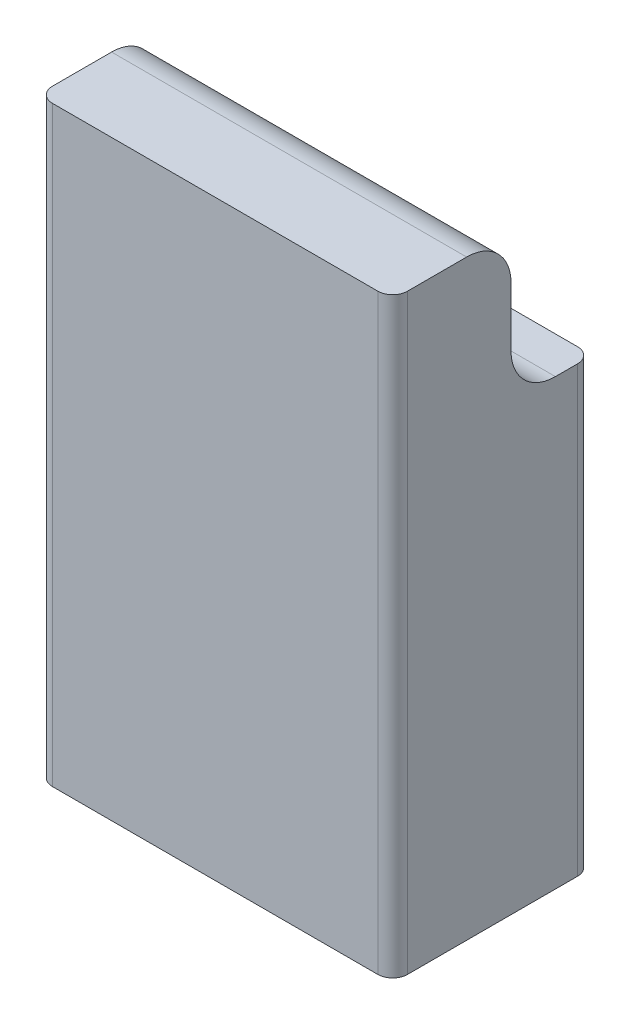
SolidWorks part; units mm, degrees
material "K110"
ref_plane "Front Plane" through (0, 0, 0) normal (0, 0, 1) x (1, 0, 0)
ref_plane "Top Plane" through (0, 0, 0) normal (0, 1, 0) x (1, 0, 0)
ref_plane "Right Plane" through (0, 0, 0) normal (1, 0, 0) x (0, 0, -1)
sketch "Sketch1" plane through (0, 0, 0) normal (0, 1, 0) x (1, 0, 0)
  line L1 (-12, -6.75) -> (12, -6.75)
  line L2 (-12, -6.75) -> (-12, 6.75)
  line L3 (-12, 6.75) -> (12, 6.75)
  line L4 (12, -6.75) -> (12, 6.75)
  line L5 (-12, -6.75) -> (12, 6.75) construction
  line L6 (-12, 6.75) -> (12, -6.75) construction
  point P0 (0, 0)
  dimension "D1" = 13.5
  dimension "D2" = 24
extrude "Boss-Extrude1" add sketch "Sketch1" against normal blind 40
sketch "Sketch2" plane through (12, 0, 0) normal (1, 0, 0) x (0, 0, -1)
  line L0 (-6.75, 0) -> (6.75, 0) construction
  line L1 (1.25, 0) -> (6.75, 0)
  line L2 (1.25, 0) -> (1.25, -7)
  line L3 (4.25, -10) -> (6.75, -10)
  line L4 (6.75, 0) -> (6.75, -10)
  line L5 (6.75, -40) -> (6.75, 0) construction
  line L6 (-6.75, -40) -> (-6.75, 0) construction
  arc A0 (1.25, -7) -> (4.25, -10) centre (4.25, -7) ccw
  dimension "D3" = 3
  dimension "D1" = 8
  dimension "D2" = 10
extrude "Cut-Extrude1" cut sketch "Sketch2" against normal up to next
fillet "Fillet1" radius 3 1 edges at (0, 0, -1.25)
fillet "Fillet2" radius 1 4 edges at (-12, -20, 6.75) (12, -20, 6.75) (-12, -25, -6.75) (12, -25, -6.75)
hole_wizard "M6 Tapped Hole1" positions "Sketch5" profile "Sketch4" tap size "M6" standard "ISO"
sketch "Sketch5" plane through (0, -40, 0) normal (0, -1, 0) x (-1, 0, 0)
  point P0 (0, 0)
sketch "Sketch4" plane through (0, -40, 0) normal (1, 0, 0) x (0, 0, -1)
  line L0 (0, 0) -> (0, 18.5022)
  line L1 (0, 18.5022) -> (2.5, 17)
  line L2 (2.5, 17) -> (2.5, 0.525)
  line L3 (2.5, 0.525) -> (3.025, 0)
  line L5 (3.025, 0) -> (0, 0)
  line L6 (-2.5, 0.525) -> (-3.025, 0) construction
  line L10 (0, 18.5022) -> (-2.5, 17) construction
  line L11 (0, -6.35) -> (0, 107.95) construction
  dimension "Tap Drill Dia." = 5
  dimension "Tap Drill Depth" = 17
  dimension "Near C'Sink Dia." = 6.05
  dimension "Near C'Sink Angle" = 90
  dimension "Drill Angle" = 118
cosmetic thread "Hole Thread1"
